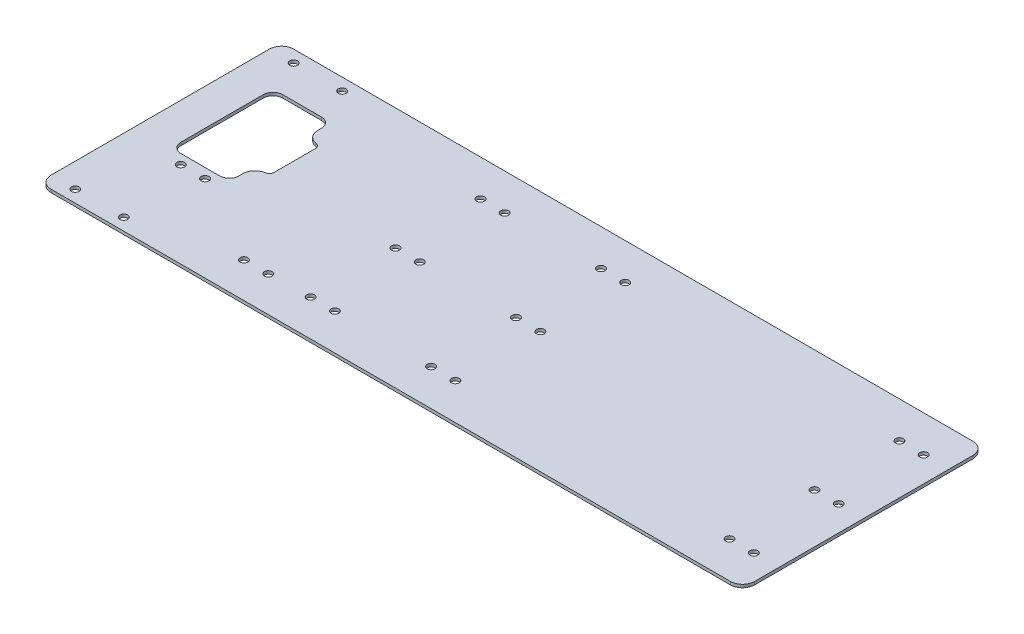
SolidWorks part; units mm, degrees
ref_plane "Front Plane" through (0, 0, 0) normal (0, 0, 1) x (1, 0, 0)
ref_plane "Top Plane" through (0, 0, 0) normal (0, 1, 0) x (1, 0, 0)
ref_plane "Right Plane" through (0, 0, 0) normal (1, 0, 0) x (0, 0, -1)
sketch "Sketch1" plane through (0, 0, 0) normal (0, 1, 0) x (1, 0, 0)
  line L0 (171.0189, 63.5) -> (171.0189, 44.45) construction
  line L1 (184.15, 63.5) -> (-184.15, 63.5)
  line L2 (184.15, 63.5) -> (184.15, -63.5)
  line L3 (184.15, -63.5) -> (-184.15, -63.5)
  line L4 (-184.15, 63.5) -> (-184.15, -63.5)
  line L5 (184.15, 63.5) -> (-184.15, -63.5) construction
  line L6 (184.15, -63.5) -> (-184.15, 63.5) construction
  line L7 (-128.2684, -0.635) -> (-128.2684, 31.115) construction
  line L8 (-128.2684, 31.115) -> (-134.6184, 31.115) construction
  line L9 (-128.2684, 5.715) -> (-134.6184, 5.715) construction
  line L12 (-165.0984, -13.335) -> (-165.0984, 40.005)
  line L15 (-134.6184, -13.335) -> (-165.0984, -13.335)
  line L17 (-134.6184, 40.005) -> (-165.0984, 40.005)
  line L18 (0, 63.5) -> (0, -63.5) construction
  line L19 (-134.6184, 40.005) -> (-134.6184, -13.335)
  line L20 (171.0189, 44.45) -> (184.15, 44.45) construction
  line L21 (0, 0) -> (-126.9984, 0) construction
  line L22 (-82.55, -45.0215) -> (-95.25, -45.0215) construction
  line L23 (171.0189, 44.45) -> (171.0189, 0) construction
  line L25 (171.0189, 0) -> (171.0189, -44.45) construction
  line L26 (171.0189, 44.45) -> (158.3189, 44.45) construction
  line L30 (171.0189, 0) -> (158.3189, 0) construction
  line L31 (171.0189, -44.45) -> (158.3189, -44.45) construction
  line L32 (158.3189, 44.45) -> (14.8089, 44.45) construction
  line L33 (14.8089, 44.45) -> (14.8089, 0) construction
  line L34 (14.8089, 0) -> (14.8089, -44.45) construction
  line L35 (-146.05, -57.15) -> (-184.15, -57.15) construction
  line L36 (-146.05, 57.15) -> (-184.15, 57.15) construction
  line L37 (-128.2684, -0.635) -> (-128.2684, 5.715) construction
  line L38 (-184.15, -18.415) -> (-154.94, -18.415) construction
  line L39 (-154.94, -18.415) -> (-142.24, -18.415) construction
  line L40 (-134.6184, 26.67) -> (-126.9984, 26.67)
  line L41 (-126.9984, 26.67) -> (-126.9984, 0)
  line L42 (-126.9984, 0) -> (-134.6184, 0)
  line L43 (14.8089, 44.45) -> (2.1089, 44.45) construction
  line L44 (14.8089, 0) -> (2.1089, 0) construction
  line L45 (14.8089, -44.45) -> (2.1089, -44.45) construction
  line L46 (2.1089, 44.45) -> (-48.2678, 44.45) construction
  line L47 (-48.2678, 44.45) -> (-60.9678, 44.45) construction
  line L48 (-48.2678, 44.45) -> (-48.2678, 0) construction
  line L49 (-48.2678, 0) -> (-60.9678, 0) construction
  line L50 (-48.2678, 0) -> (-48.2678, -44.45) construction
  line L51 (-48.2678, -44.45) -> (-60.9678, -44.45) construction
  circle A12 centre (-146.05, -57.15) radius 2.032
  circle A13 centre (-171.45, -57.15) radius 2.032
  circle A14 centre (-146.05, 57.15) radius 2.032
  circle A15 centre (-171.45, 57.15) radius 2.032
  circle A18 centre (-154.94, -18.415) radius 2.032
  circle A19 centre (-142.24, -18.415) radius 2.032
  circle A20 centre (-95.25, -45.0215) radius 2.032
  circle A21 centre (-82.55, -45.0215) radius 2.032
  circle A24 centre (171.0189, 44.45) radius 2.032
  circle A25 centre (171.0189, 0) radius 2.032
  circle A26 centre (171.0189, -44.45) radius 2.032
  circle A27 centre (158.3189, 44.45) radius 2.032
  circle A28 centre (158.3189, 0) radius 2.032
  circle A29 centre (158.3189, -44.45) radius 2.032
  circle A30 centre (2.1089, 44.45) radius 2.032
  circle A31 centre (2.1089, 0) radius 2.032
  circle A32 centre (2.1089, -44.45) radius 2.032
  circle A33 centre (14.8089, -44.45) radius 2.032
  circle A34 centre (14.8089, 0) radius 2.032
  circle A35 centre (14.8089, 44.45) radius 2.032
  circle A36 centre (-60.9678, 44.45) radius 2.032
  circle A37 centre (-48.2678, 44.45) radius 2.032
  circle A38 centre (-60.9678, 0) radius 2.032
  circle A39 centre (-60.9678, -44.45) radius 2.032
  circle A40 centre (-48.2678, -44.45) radius 2.032
  circle A41 centre (-48.2678, 0) radius 2.032
  point P0 (0, 0)
  point P11 (-128.2684, -0.635)
  point P13 (-134.6184, 31.115)
  point P17 (-134.6184, 5.715)
  point P37 (0, 0)
  dimension "D5" = 13.335
  dimension "D6" = 29.21
  dimension "D18" = 12.7
  dimension "D13" = 4.064
  dimension "D23" = 44.45
  dimension "D24" = 44.45
  dimension "D31" = 12.7
  dimension "D32" = 143.51
  dimension "D35" = 50.3767
  dimension "D1" = 368.3
  dimension "D2" = 127
  dimension "D3" = 128.27
  dimension "D4" = 25.4
  dimension "D7" = 6.35
  dimension "D8" = 30.48
  dimension "D9" = 53.34
  dimension "D10" = 8.89
  dimension "D11" = 19.05
  dimension "D12" = 12.7
  dimension "D14" = 38.1
  dimension "D15" = 6.35
  dimension "D16" = 12.7
  dimension "D17" = 6.35
  dimension "D19" = 31.75
  dimension "D20" = 19.05
  dimension "D21" = 13.1311
  dimension "D22" = 5.08
  dimension "D25" = 88.9
  dimension "D26" = 12.7
  dimension "D27" = 7.62
  dimension "D28" = 26.67
  dimension "D29" = 13.335
  dimension "D30" = 18.4785
  dimension "D33" = 44.45
  dimension "D34" = 44.45
extrude "Boss-Extrude1" add sketch "Sketch1" along normal blind 1.5875 contours L1 L4 L3 L2 A21 A20 A18 A14 A12 L41 L42 L19 L15 L12 L17 L40 A13 A15 A19 region at (6.1738, 0, 0.5099)
sketch "Sketch2" [suppressed] plane through (0, 1.5875, 0) normal (0, 1, 0) x (1, 0, 0)
  line L0 (-69.85, 63.5) -> (-69.85, -63.5)
  line L1 (184.15, 63.5) -> (-184.15, 63.5) construction
  line L2 (184.15, -63.5) -> (-184.15, -63.5) construction
  circle A0 centre (-82.55, -45.0215) radius 2.032 construction
  circle M9 centre (146.05, 57.15) radius 2.032
  circle M10 centre (171.45, 57.15) radius 2.032
  circle M11 centre (146.05, -57.15) radius 2.032
  circle M12 centre (171.45, -57.15) radius 2.032
  line M13 (184.15, 63.5) -> (-184.15, 63.5)
  line M15 (-184.15, -63.5) -> (184.15, -63.5)
  line M16 (184.15, -63.5) -> (184.15, 63.5)
  dimension "D1" = 12.7
extrude "Cut-Extrude1" [suppressed] cut sketch "Sketch2" against normal through all flip side to cut contours L0 M13 M15 M16 M10 M12 M11 M9
fillet "Fillet1" radius 5.08 4 edges at (-134.6184, 0.7937, 13.335) (-165.0984, 0.7937, 13.335) (-165.0984, 0.7937, -40.005) (-134.6184, 0.7937, -40.005)
fillet "Fillet3" radius 6.35 4 edges at (184.15, 0.7937, 63.5) (184.15, 0.7937, -63.5) (-184.15, 0.7937, 63.5) (-184.15, 0.7937, -63.5)
fillet "Fillet4" radius 2.54 2 edges at (-126.9984, 0.7937, 0) (-126.9984, 0.7937, -26.67)
fillet "Fillet5" radius 6.35 2 edges at (-134.6184, 0.7937, 0) (-134.6184, 0.7937, -26.67)
fillet "Fillet6" [suppressed] radius 6.35
sketch "Sketch3" plane through (0, 1.5875, 0) normal (0, 1, 0) x (1, 0, 0)
  circle A0 centre (25.4, -25.4) radius 2.032
  circle A1 centre (25.4, 25.4) radius 2.032
  arc A2 (10.7648, -26.0196) -> (10.7648, -24.7804) centre (12.7, -25.4) ccw construction
  circle A3 centre (25.4, -25.4) radius 2.032 construction
  circle A4 centre (25.4, 25.4) radius 2.032 construction
  arc A5 (10.7648, 24.7804) -> (10.7648, 26.0196) centre (12.7, 25.4) ccw construction
  arc A6 (10.7648, 24.7804) -> (10.7648, 26.0196) centre (12.7, 25.4) ccw
  arc A7 (10.7648, -26.0196) -> (10.7648, -24.7804) centre (12.7, -25.4) ccw
  circle A9 centre (162.56, -44.45) radius 2.032 construction
  circle A10 centre (162.56, 44.45) radius 2.032 construction
  circle A12 centre (-2.54, -25.4) radius 2.032 construction
  circle A15 centre (-73.66, 44.45) radius 2.032 construction
  circle A16 centre (-73.66, -44.45) radius 2.032 construction
  circle A17 centre (25.4, -25.4) radius 2.032
  circle A18 centre (25.4, 25.4) radius 2.032
  circle A19 centre (-15.24, -25.4) radius 2.032 construction
  circle A20 centre (-15.24, 25.4) radius 2.032 construction
  circle A23 centre (162.56, -44.45) radius 2.032
  circle A24 centre (162.56, 44.45) radius 2.032
  circle A29 centre (12.7, -25.4) radius 2.032
  circle A31 centre (12.7, 25.4) radius 2.032
  circle A32 centre (175.26, 44.45) radius 2.032 construction
  circle A33 centre (175.26, -44.45) radius 2.032 construction
  circle A34 centre (175.26, 44.45) radius 2.032
  circle A35 centre (175.26, -44.45) radius 2.032
  circle A36 centre (-2.54, 25.4) radius 2.032 construction
  circle A41 centre (-2.54, -25.4) radius 2.032
  circle A42 centre (-2.54, 25.4) radius 2.032
  circle A54 centre (-73.66, 44.45) radius 2.032
  circle A55 centre (-73.66, -44.45) radius 2.032
  circle A56 centre (-15.24, -25.4) radius 2.032
  circle A57 centre (-15.24, 25.4) radius 2.032
extrude "Cut-Extrude5" [suppressed] cut sketch "Sketch3" against normal through all contours A55 | A54 | A57 | A56 | A41 | A0 | A42 | A31 | A29 | A1
equation "\".80.55in\"=0.55"
